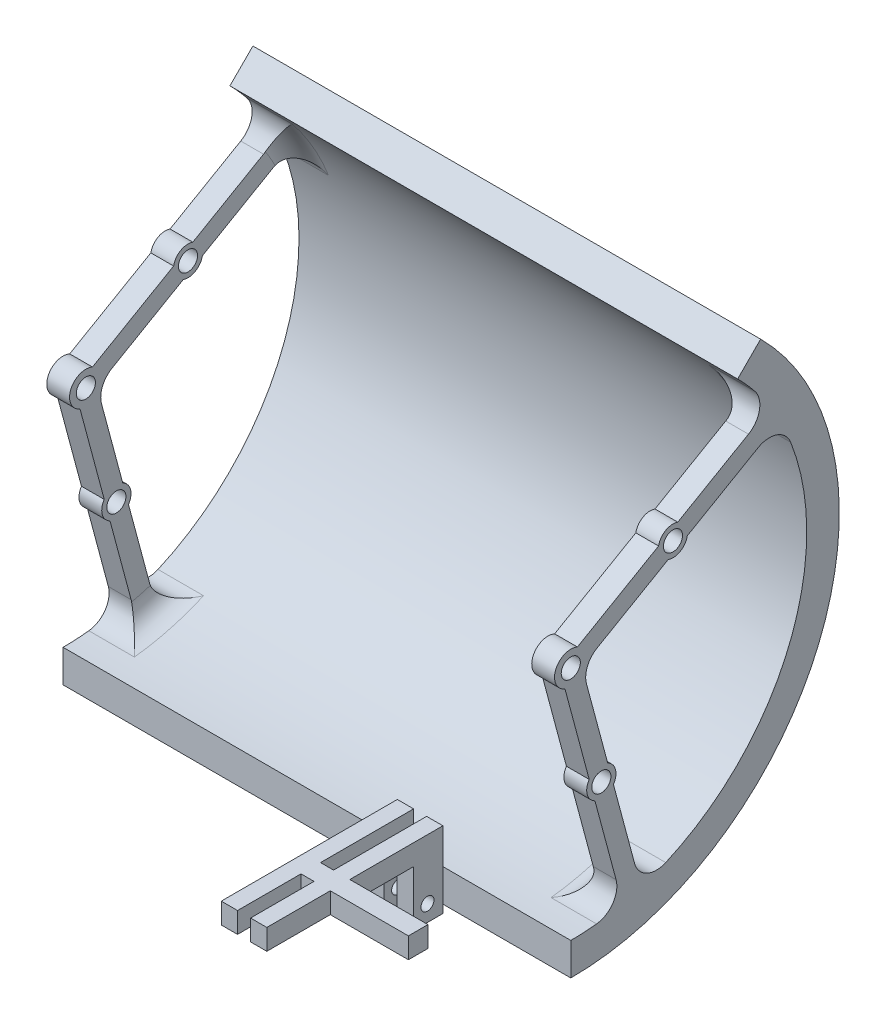
SolidWorks part; units mm, degrees
ref_plane "Front Plane" through (0, 0, 0) normal (0, 0, 1) x (1, 0, 0)
ref_plane "Top Plane" through (0, 0, 0) normal (0, 1, 0) x (1, 0, 0)
ref_plane "Right Plane" through (0, 0, 0) normal (1, 0, 0) x (0, 0, -1)
sketch "Sketch1" plane through (0, 0, 0) normal (0, 0, 1) x (1, 0, 0)
  line L0 (0, 41.25) -> (80.29, 41.25) construction
  line L1 (0, 0) -> (78.006, 0)
  line L2 (0, 0) -> (0, 5)
  line L3 (0, 5) -> (78.006, 5)
  line L4 (78.006, 0) -> (78.006, 5)
  dimension "D1" = 5
  dimension "D2" = 78.006
  dimension "D3" = 36.25
revolve "Revolve1" add sketch "Sketch1" angle 135 about L0
sketch "Sketch3" plane through (0, 0, 0) normal (1, 0, 0) x (0, 0, -1)
  line L0 (7.9546, 5.8835) -> (3.7121, 21.7168)
  line L1 (1.7119, 40.5409) -> (5.6701, 25.7684)
  line L2 (0, 41.25) -> (9.3822, 6.2352) construction
  line L3 (30.6326, 60.6331) -> (16.4369, 52.4373)
  line L4 (32.1026, 58.087) -> (17.9069, 49.8911)
  line L5 (0, 41.25) -> (31.3934, 59.375) construction
  line L7 (0, 0) -> (0, 5) construction
  line L9 (0, 41.25) -> (9.3822, 6.2352) construction
  line L10 (0, 41.25) -> (33.4906, 27.3777) construction
  line L11 (6.5519, 22.4777) -> (10.7944, 6.6445)
  line L12 (2.8303, 25.0075) -> (-0.8965, 38.9163)
  line L13 (14.9565, 48.1877) -> (1.7119, 40.5409)
  line L14 (13.4865, 50.7339) -> (1.0162, 43.5341)
  arc A0 (0, 5) -> (25.6326, 66.8826) centre (0, 41.25) ccw construction
  arc A3 (30.6326, 60.6331) -> (32.1026, 58.087) centre (0, 41.25) cw
  arc A4 (10.7944, 6.6445) -> (7.9546, 5.8835) centre (0, 41.25) cw
  arc A5 (-0.8965, 38.9163) -> (1.0162, 43.5341) centre (0, 41.25) cw
  arc A8 (6.5519, 22.4777) -> (5.6701, 25.7684) centre (4.6911, 23.7426) ccw
  arc A9 (17.9069, 49.8911) -> (14.9565, 48.1877) centre (15.6967, 50.3125) cw
  arc A10 (2.8303, 25.0075) -> (3.7121, 21.7168) centre (4.6911, 23.7426) ccw
  arc A11 (13.4865, 50.7339) -> (16.4369, 52.4373) centre (15.6967, 50.3125) cw
  point P21 (9.3822, 6.2352)
  dimension "D5" = 2.5
  dimension "D6" = 4.5
  dimension "D1" = 1.47
  dimension "D2" = 15
  dimension "D3" = 1.47
  dimension "D4" = 105
extrude "Boss-Extrude1" add sketch "Sketch3" along normal blind 3.5
sketch "Sketch5" plane through (3.5, 0, 0) normal (1, 0, 0) x (0, 0, -1)
  circle A0 centre (0, 41.25) radius 1.47
  circle A1 centre (4.6911, 23.7426) radius 1.47
  arc A2 (2.8303, 25.0075) -> (3.7121, 21.7168) centre (4.6911, 23.7426) ccw construction
  circle A3 centre (15.6967, 50.3125) radius 1.47
  arc A4 (14.9565, 48.1877) -> (17.9069, 49.8911) centre (15.6967, 50.3125) ccw construction
  dimension "D1" = 2.94
  dimension "D2" = 2.94
  dimension "D3" = 2.94
extrude "Cut-Extrude1" cut sketch "Sketch5" against normal through all
ref_plane "Plane1" through (39.003, 0, 0) normal (1, 0, 0) x (0, 0, -1)
mirror "Mirror1" about plane through (39.003, 0, 0) normal (1, 0, 0) of "Boss-Extrude1"
fillet "Fillet1" radius 3.5 12 edges at (76.256, 58.087, -32.1026) (74.506, 59.375, -31.3934) (76.256, 60.6331, -30.6326) (76.256, 6.6445, -10.7944) (74.506, 6.2352, -9.3822) (76.256, 5.8835, -7.9546) (1.75, 58.087, -32.1026) (3.5, 59.375, -31.3934) (1.75, 60.6331, -30.6326) (1.75, 6.6445, -10.7944) (3.5, 6.2352, -9.3822) (1.75, 5.8835, -7.9546)
fillet "Fillet2" radius 3.5 2 edges at (76.256, 40.5409, -1.7119) (1.75, 40.5409, -1.7119)
mirror "Mirror2" about plane through (39.003, 0, 0) normal (1, 0, 0) of "Cut-Extrude1"
sketch "Sketch6" plane through (0, 0, 0) normal (0, 0, 1) x (1, 0, 0)
  line L0 (59.6021, 2.5) -> (78.006, 2.5) construction
  line L5 (54.856, -7.9) -> (54.856, 3.7) construction
  line L6 (59.6021, 2.5) -> (64.0715, 2.5) construction
  line L7 (78.006, 5) -> (0, 5) construction
  line L8 (0, 5) -> (0, 0) construction
  line L9 (0, 2.5) -> (64.0715, 2.5) construction
  line L10 (78.006, 0) -> (78.006, 5) construction
  line L29 (53.856, -1.25) -> (51.356, -1.25)
  line L30 (53.856, -1.25) -> (53.856, 10.43)
  line L31 (53.856, 10.43) -> (51.356, 10.43)
  line L32 (51.356, -1.25) -> (51.356, 10.43)
  line L34 (55.856, -1.25) -> (58.356, -1.25)
  line L35 (55.856, -1.25) -> (55.856, 10.43)
  line L36 (55.856, 10.43) -> (58.356, 10.43)
  line L37 (58.356, -1.25) -> (58.356, 10.43)
  line L38 (0, 0) -> (78.006, 0) construction
  dimension "D1" = 22.15
  dimension "D2" = 2.5
  dimension "D3" = 1.25
  dimension "D4" = 2
  dimension "D5" = 1.25
  dimension "D6" = 5.43
extrude "Boss-Extrude2" add sketch "Sketch6" along normal up to vertex (4.75 mm away)
sketch "Sketch11" plane through (0, 0, 0) normal (-1, 0, 0) x (0, 0, 1)
  line L1 (-24.7218, 14.7379) -> (-31.6017, 14.7379)
  line L2 (-24.7218, 14.7379) -> (-24.7218, 10.7379)
  line L3 (-24.7218, 10.7379) -> (-31.6017, 10.7379)
  line L4 (-31.6017, 14.7379) -> (-31.6017, 10.7379)
  arc A0 (-33.7804, 54.4009) -> (-14.5872, 8.0645) centre (0, 41.25) ccw construction
  arc A1 (-29.1682, 70.4182) -> (0, 0) centre (0, 41.25) ccw construction
  dimension "D1" = 4
  dimension "D2" = 6.8799
extrude "Boss-Extrude4" add sketch "Sketch11" against normal blind 79.29
sketch "Sketch13" plane through (0, 10.7379, 0) normal (0, -1, 0) x (1, 0, 0)
  line L0 (78.006, -27.7592) -> (0, -27.7592) construction
  line L1 (22.063, -27.7592) -> (31.603, -27.7592)
  line L2 (22.063, -27.7592) -> (22.063, -31.6017)
  line L3 (22.063, -31.6017) -> (31.603, -31.6017)
  line L4 (31.603, -27.7592) -> (31.603, -31.6017)
  line L5 (79.29, -31.6017) -> (0, -31.6017) construction
  line L6 (39.003, -27.7592) -> (39.003, -31.6017) construction
  line L7 (53.913, -27.7592) -> (63.453, -27.7592)
  line L8 (53.913, -27.7592) -> (53.913, -31.6017)
  line L9 (53.913, -31.6017) -> (63.453, -31.6017)
  line L10 (63.453, -27.7592) -> (63.453, -31.6017)
  line L11 (39.003, -27.7592) -> (39.003, -31.6017) construction
  dimension "D1" = 9.54
  dimension "D2" = 9.54
  dimension "D3" = 14.91
  dimension "D4" = 7.4
extrude "Boss-Extrude5" add sketch "Sketch13" along normal blind 7.5
sketch "Sketch14" plane through (0, 0, 0) normal (-1, 0, 0) x (0, 0, 1)
  line L0 (-31.6017, 14.7379) -> (-31.6017, 10.7379) construction
  line L1 (-27.7592, 10.7379) -> (-32.6582, 9.7379)
  line L2 (-32.6582, 9.7379) -> (-31.6017, 14.7379)
  arc A0 (-27.7592, 10.7379) -> (-31.6017, 14.7379) centre (0, 41.25) cw
  dimension "D1" = 5
  dimension "D2" = 5
fillet "Fillet4" radius 4 1 edges at (42.758, 10.7379, -31.6017)
sketch "Sketch17" plane through (0, 0, -31.6017) normal (0, 0, -1) x (-1, 0, 0)
  line L0 (-22.063, 3.2379) -> (-31.603, 3.2379) construction
  line L1 (-25.243, 3.2379) -> (-28.423, 3.2379)
  line L2 (-25.243, 3.2379) -> (-25.243, 10.7379)
  line L3 (-25.243, 10.7379) -> (-28.423, 10.7379)
  line L4 (-28.423, 3.2379) -> (-28.423, 10.7379)
  line L5 (-53.913, 3.2379) -> (-63.453, 3.2379) construction
  line L6 (-57.093, 3.2379) -> (-60.273, 3.2379)
  line L7 (-57.093, 3.2379) -> (-57.093, 10.7379)
  line L8 (-57.093, 10.7379) -> (-60.273, 10.7379)
  line L9 (-60.273, 3.2379) -> (-60.273, 10.7379)
  line L10 (-53.913, 3.2379) -> (-53.913, 14.7348) construction
  line L11 (-22.063, 3.2379) -> (-22.063, 10.7379) construction
  dimension "D1" = 3.18
  dimension "D2" = 3.18
  dimension "D3" = 3.18
  dimension "D4" = 3.18
  dimension "D5" = 7.5
  dimension "D6" = 7.5
extrude "Cut-Extrude12" cut sketch "Sketch17" against normal up to surface (3.8425 mm away) up to face at (58.683, 6.9879, -27.7592)
sketch "Sketch18" plane through (22.063, 0, 0) normal (-1, 0, 0) x (0, 0, 1)
  line L0 (-27.7592, 3.2379) -> (-27.7592, 10.7379) construction
  line L1 (-27.7592, 3.2379) -> (-31.6017, 3.2379) construction
  circle A0 centre (-29.6792, 6.2379) radius 1.47
  dimension "D2" = 3
  dimension "D3" = 2.94
  dimension "D1" = 1.92
extrude "Cut-Extrude13" cut sketch "Sketch18" against normal up to surface (41.39 mm away) up to face at (63.453, 6.9879, -29.6804)
sketch "Sketch20" plane through (0, 10.43, 0) normal (0, 1, 0) x (1, 0, 0)
  line L1 (58.356, -4.55) -> (55.856, -4.55)
  line L2 (58.356, -4.55) -> (58.356, -14.3)
  line L3 (58.356, -27.05) -> (55.856, -27.05)
  line L4 (55.856, -4.55) -> (55.856, -14.3)
  line L5 (53.856, -4.55) -> (51.356, -4.55)
  line L6 (53.856, -4.55) -> (53.856, -14.3)
  line L7 (53.856, -27.05) -> (51.356, -27.05)
  line L8 (51.356, -4.55) -> (51.356, -27.05)
  line L11 (51.356, -15.8) -> (71.7407, -15.8) construction
  line L12 (55.856, -17.3) -> (53.856, -17.3)
  line L13 (55.856, -14.3) -> (53.856, -14.3)
  line L14 (58.356, -17.3) -> (58.356, -27.05)
  line L15 (58.356, -17.3) -> (70.356, -17.3)
  line L17 (58.356, -14.3) -> (70.356, -14.3)
  line L18 (70.356, -17.3) -> (70.356, -14.3)
  line L19 (55.856, -17.3) -> (55.856, -27.05)
  line L20 (53.856, -17.3) -> (53.856, -27.05)
  dimension "D1" = 22.5
  dimension "D2" = 1.5
  dimension "D3" = 1.5
  dimension "D4" = 12
  dimension "D5" = 11.25
extrude "Boss-Extrude6" add sketch "Sketch20" against normal blind 3.18
sketch "Sketch21" plane through (0, 10.7379, 0) normal (0, -1, 0) x (1, 0, 0)
  line L1 (78.006, -24.7218) -> (79.29, -24.7218)
  line L2 (78.006, -24.7218) -> (78.006, -31.6017)
  line L3 (78.006, -31.6017) -> (79.29, -31.6017)
  line L4 (79.29, -24.7218) -> (79.29, -31.6017)
extrude "Cut-Extrude14" cut sketch "Sketch21" against normal through all
extrude "Cut-Extrude15" cut sketch "Sketch14" against normal up to surface (22.063 mm away) contours L1 L2 A0 up to face at (22.063, 6.2379, -28.2092)
sketch "Sketch23" plane through (78.006, 0, 0) normal (1, 0, 0) x (0, 0, -1)
  line L0 (31.6017, 14.7379) -> (31.6017, 10.7379) construction
  line L1 (27.7592, 10.7379) -> (34.5089, 8.0995)
  line L2 (34.5089, 8.0995) -> (31.6017, 14.7379)
  arc A0 (27.7592, 10.7379) -> (31.6017, 14.7379) centre (0, 41.25) ccw
  dimension "D1" = 45
extrude "Cut-Extrude16" cut sketch "Sketch23" against normal up to surface (14.553 mm away) up to face at (63.453, 6.2379, -28.2092)
sketch "Sketch25" plane through (53.856, 0, 0) normal (1, 0, 0) x (0, 0, -1)
  line L0 (-4.55, -1.25) -> (0, -1.25) construction
  line L1 (-4.55, -1.25) -> (-4.55, 7.25) construction
  circle A0 centre (-2.375, 1.25) radius 1
  dimension "D3" = 2
  dimension "D1" = 2.5
  dimension "D2" = 2.175
extrude "Cut-Extrude17" cut sketch "Sketch25" against normal through all both and the other way through all
